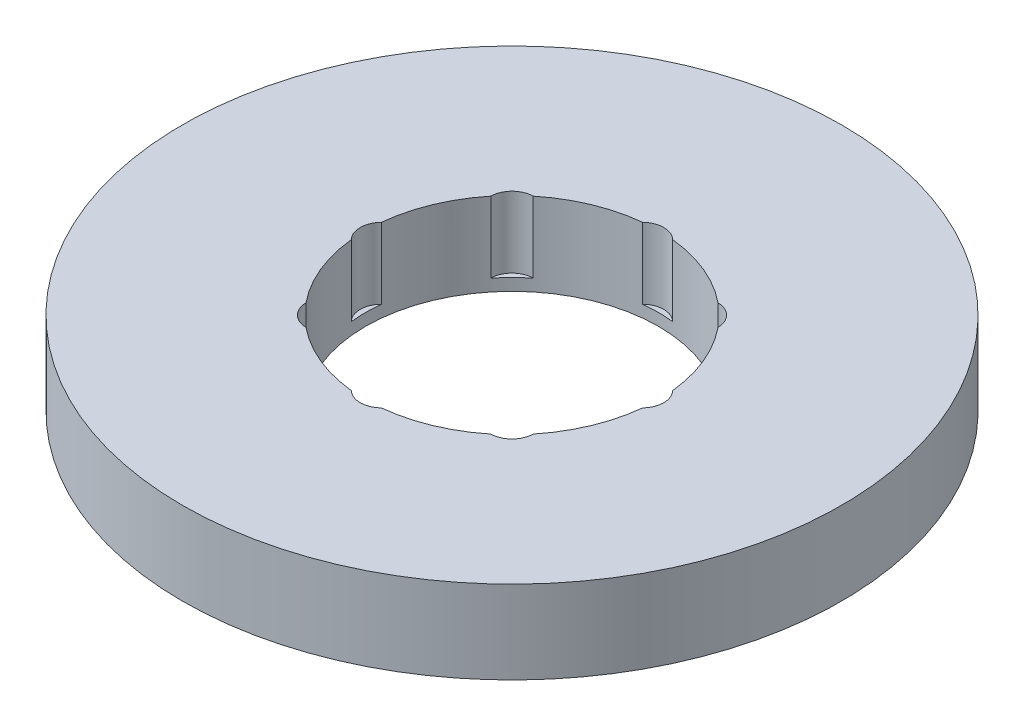
SolidWorks part; units mm, degrees
ref_plane "Front Plane" through (0, 0, 0) normal (0, 0, 1) x (1, 0, 0)
ref_plane "Top Plane" through (0, 0, 0) normal (0, 1, 0) x (1, 0, 0)
ref_plane "Right Plane" through (0, 0, 0) normal (1, 0, 0) x (0, 0, -1)
sketch "Sketch1" plane through (0, 0, 0) normal (0, 1, 0) x (1, 0, 0)
  circle A0 centre (0, 0) radius 67.5
  dimension "FLANGE_OD" = 135
extrude "Boss-Extrude1" add sketch "Sketch1" along normal blind 17
sketch "Sketch2" plane through (0, 0, 0) normal (0, 1, 0) x (1, 0, 0)
  circle A0 centre (0, 0) radius 30
  dimension "BORE_D" = 60
extrude "Cut-Extrude1" cut sketch "Sketch2" along normal through all
sketch "Sketch3" plane through (0, 17, 0) normal (0, 1, 0) x (1, 0, 0)
  circle A0 centre (0, 0) radius 26.6588 construction
  circle A1 centre (-26.6588, 0) radius 4.4269
  dimension "BOLT_D" = 8.8538
  dimension "BOLT_PCD" = 53.3176
extrude "Cut-Extrude2" cut sketch "Sketch3" against normal blind 14.5362
pattern_circular "CirPattern1" count 8 over 360 about axis through (0, 0, 0) along (0, 1, 0) of "Cut-Extrude2"
